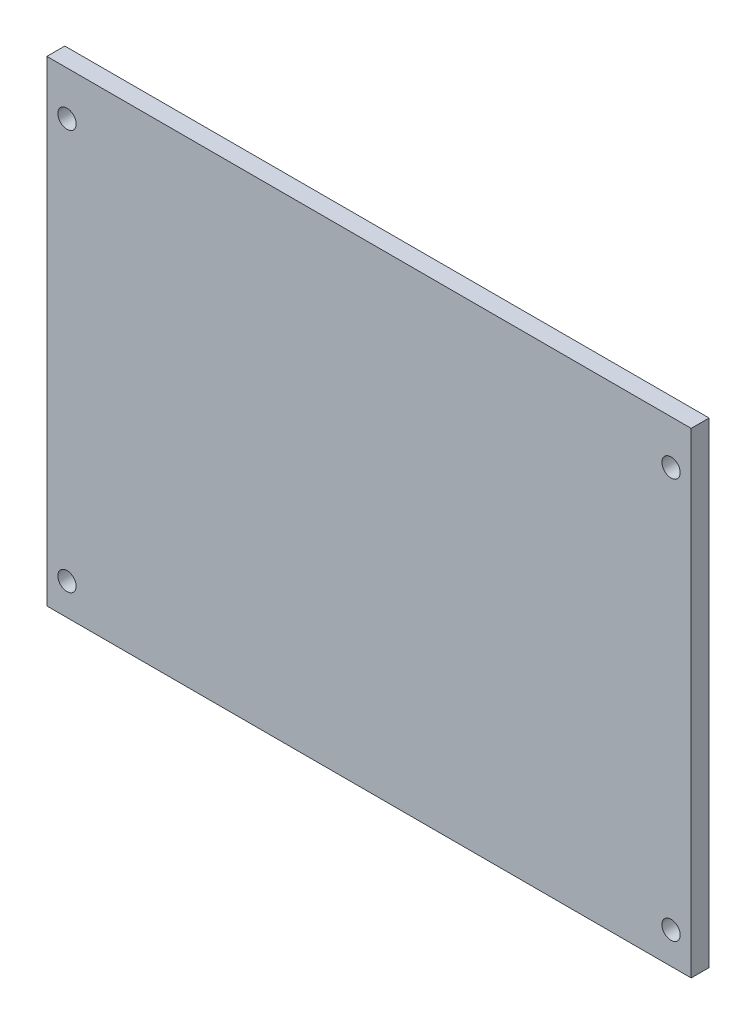
SolidWorks part; units mm, degrees
ref_plane "Front Plane" through (0, 0, 0) normal (0, 0, 1) x (1, 0, 0)
ref_plane "Top Plane" through (0, 0, 0) normal (0, 1, 0) x (1, 0, 0)
ref_plane "Right Plane" through (0, 0, 0) normal (1, 0, 0) x (0, 0, -1)
sketch "Sketch1" plane through (0, 0, 0) normal (0, 1, 0) x (1, 0, 0)
  circle A0 centre (0, 0) radius 172.5
  dimension "D1" = 345
extrude "Boss-Extrude1" add sketch "Sketch1" along normal blind 10
sketch "Sketch2" plane through (0, 10, 0) normal (0, 1, 0) x (1, 0, 0)
  circle A0 centre (-75.91, -178.72) radius 48.41
  circle A1 centre (75.91, -178.72) radius 48.41
  dimension "D1" = 96.82
  dimension "D2" = 96.82
  dimension "D3" = 151.82
  dimension "D4" = 0
  dimension "D5" = 178.72
  dimension "D6" = 75.91
extrude "Cut-Extrude1" cut sketch "Sketch2" against normal blind 10
sketch "Sketch3" plane through (0, 10, 0) normal (0, 1, 0) x (1, 0, 0)
  line L0 (-75.91, -178.72) -> (75.91, -178.72)
  line L1 (-98.9683, -119.81) -> (98.9683, -119.81)
  line L2 (0, -178.72) -> (0, -205.4095)
  line L3 (0, -116.81) -> (0, -103.1109)
  line L4 (-97.8835, -116.81) -> (97.8835, -116.81)
  arc A0 (97.8835, -116.81) -> (-97.8835, -116.81) centre (0, 0) ccw
  arc A1 (98.9683, -119.81) -> (-98.9683, -119.81) centre (0, 0) ccw
  dimension "D1" = 304.8
  dimension "D2" = 3
  dimension "D4" = 0
extrude "Boss-Extrude2" add sketch "Sketch3" along normal blind 5 contours L1 A1 A0 L4 region at (0, 10, -154.9849)
sketch "Sketch4" plane through (0, 10, 0) normal (0, 1, 0) x (1, 0, 0)
  line L0 (-28.2612, -170.1692) -> (28.2612, -170.1692)
  line L1 (28.2612, -170.1692) -> (28.2612, -183.8361)
  line L2 (28.2612, -183.8361) -> (-30.3005, -183.8361)
  line L3 (-30.3005, -183.8361) -> (-28.2612, -170.1692)
extrude "Cut-Extrude2" cut sketch "Sketch4" against normal blind 497
sketch "Sketch5" plane through (0, 10, 0) normal (0, 1, 0) x (1, 0, 0)
  line L0 (-166.525, 159.566) -> (-166.525, -120.1627)
  line L1 (166.525, 178.4393) -> (166.525, -124.881)
  line L2 (-148.2899, 170.4208) -> (120.6541, 170.4208)
  line L3 (28.2612, -170.1692) -> (-28.2612, -170.1692) construction
  line L5 (-166.525, 170.4208) -> (166.525, 170.4208)
  line L6 (-166.525, 170.4208) -> (-166.525, -186.2191)
  line L7 (-166.525, -186.2191) -> (166.525, -186.2191)
  line L8 (166.525, 170.4208) -> (166.525, -186.2191)
  line L9 (-215.4787, 226.3504) -> (214.5081, 226.3504)
  line L10 (-215.4787, 226.3504) -> (-215.4787, -259.9327)
  line L11 (-215.4787, -259.9327) -> (214.5081, -259.9327)
  line L12 (214.5081, 226.3504) -> (214.5081, -259.9327)
  arc M6 (102.8405, -138.4922) -> (-102.8405, -138.4922) centre (0, 0) ccw
  dimension "D1" = 333.05
  dimension "D2" = 166.525
  dimension "D3" = 340.59
extrude "Cut-Extrude6" cut sketch "Sketch5" against normal blind 497 contours L2 M6 | L1 M6 | L0 M6 region at (-168.9186, 10, 0) region at (0, 10, -171.2529) region at (168.9186, 10, 0)
sketch "Sketch6" plane through (0, 10, 0) normal (0, 1, 0) x (1, 0, 0)
  line L0 (-97.8835, -116.81) -> (97.8835, -116.81)
  line L1 (-97.8835, -116.81) -> (-97.8835, -61.81)
  line L2 (97.8835, -116.81) -> (97.8835, -61.81)
  line L3 (97.8835, -61.81) -> (-97.8835, -61.81)
  line L4 (92.8835, -66.81) -> (-92.8835, -66.81)
  line L5 (-92.8835, -111.81) -> (-92.8835, -66.81)
  line L6 (-92.8835, -111.81) -> (92.8835, -111.81)
  line L7 (92.8835, -111.81) -> (92.8835, -66.81)
  dimension "D1" = 55
  dimension "D2" = 5
extrude "Boss-Extrude3" add sketch "Sketch6" along normal blind 133.35
sketch "Sketch7" plane through (0, 10, 0) normal (0, 1, 0) x (1, 0, 0)
  line L1 (-92.8835, -66.81) -> (92.8835, -66.81)
  line L2 (-92.8835, -66.81) -> (-92.8835, -111.81)
  line L3 (-92.8835, -111.81) -> (92.8835, -111.81)
  line L4 (92.8835, -66.81) -> (92.8835, -111.81)
extrude "Boss-Extrude4" add sketch "Sketch7" along normal blind 5
sketch "Sketch8" plane through (0, 10, 0) normal (0, 1, 0) x (1, 0, 0)
  line L0 (-112.8835, -61.81) -> (-112.8835, -101.2671)
  line L1 (-97.8835, -61.81) -> (97.8835, -61.81)
  line L2 (-97.8835, -61.81) -> (-97.8835, -115.8298)
  line L4 (97.8835, -61.81) -> (97.8835, -115.8298)
  line L6 (112.8835, -46.81) -> (112.8835, -101.2671)
  line L7 (-88.0285, -46.81) -> (112.8835, -46.81)
  line L8 (-112.8835, -46.81) -> (-112.8835, -131.81) construction
  line L9 (-112.8835, -131.81) -> (112.8835, -131.81) construction
  line L10 (112.8835, -46.81) -> (112.8835, -131.81) construction
  line L11 (74.9923, -131.81) -> (76.4976, -131.81)
  line L12 (-97.8835, -116.81) -> (97.8835, -116.81) construction
  line L13 (97.8835, -61.81) -> (97.8835, -116.81) construction
  line L14 (-97.8835, -61.81) -> (-97.8835, -116.81) construction
  line L15 (-112.8835, -46.81) -> (112.8835, -46.81) construction
  line L18 (-112.8835, -61.81) -> (-88.0285, -61.81)
  line L19 (-88.0285, -46.81) -> (-88.0285, -61.81)
  arc A1 (-112.8835, -101.2671) -> (-96.7117, -116.81) centre (0, 0) ccw
  arc A5 (97.8835, -115.8298) -> (112.8835, -101.2671) centre (0, 0) ccw
  line M3 (-97.8835, -116.81) -> (-97.8835, -61.81)
  line M5 (97.8835, -61.81) -> (97.8835, -116.81)
  dimension "D1" = 15
extrude "Boss-Extrude5" add sketch "Sketch8" along normal blind 8 contours L0 A1 L18 M3 | A5 L6 L7 L19 L1 M5 region at (-104.9975, 10, 85.5341) region at (29.9995, 10, 60.2371)
chamfer "Chamfer1" distance 8 angle 38 3 edges at (-97.8835, 18, 88.8199) (4.9275, 18, 61.81) (97.8835, 18, 88.8199) first distance on face at (-97.8835, 51.1, 100.8157) first distance on face at (-50.228, 47.3375, 61.81) first distance on face at (97.8835, 51.1, 100.8157)
fillet "Fillet1" radius 38 3 edges at (-97.8835, 26, 88.8199) (4.9275, 26, 61.81) (97.8835, 26, 88.8199)
sketch "Sketch9" plane through (0, 10, 0) normal (0, 1, 0) x (1, 0, 0)
  circle A0 centre (0, 0) radius 374.0793
extrude "Cut-Extrude7" cut sketch "Sketch9" against normal blind 93
sketch "Sketch10" plane through (0, 10, 0) normal (0, -1, 0) x (1, 0, 0)
  circle A0 centre (0, 0) radius 152.4
  circle A1 centre (0, 0) radius 229.3861
extrude "Cut-Extrude8" cut sketch "Sketch10" against normal blind 93 and the other way blind 93
sketch "Sketch11" plane through (0, 143.35, 0) normal (0, 1, 0) x (1, 0, 0)
  line L0 (47.0835, -61.81) -> (47.0835, -116.81)
  line L1 (97.8835, -61.81) -> (-97.8835, -61.81) construction
  line L2 (-97.8835, -116.81) -> (97.8835, -116.81) construction
  line L3 (97.8835, -116.81) -> (97.8835, -61.81) construction
  line L4 (47.0835, -61.81) -> (-97.8835, -61.81)
  line L5 (-97.8835, -61.81) -> (-97.8835, -116.81)
  line L6 (-97.8835, -116.81) -> (47.0835, -116.81)
  line L8 (-140.8808, -21.3721) -> (150.5625, -21.3721)
  line L9 (-140.8808, -21.3721) -> (-140.8808, -156.1708)
  line L10 (-140.8808, -156.1708) -> (150.5625, -156.1708)
  line L11 (150.5625, -21.3721) -> (150.5625, -156.1708)
  dimension "D1" = 50.8
extrude "Cut-Extrude9" cut sketch "Sketch11" against normal blind 143
sketch "Sketch12" plane through (0, 143.35, 0) normal (0, 1, 0) x (1, 0, 0)
  line L1 (47.0835, -61.81) -> (52.0835, -61.81)
  line L2 (47.0835, -61.81) -> (47.0835, -116.81)
  line L3 (47.0835, -116.81) -> (52.0835, -116.81)
  line L4 (52.0835, -61.81) -> (52.0835, -116.81)
  dimension "D1" = 5
extrude "Boss-Extrude6" add sketch "Sketch12" against normal up to surface (133.35 mm away) up to face at (-25.4, 10, 89.31)
sketch "Sketch13" plane through (-97.8835, 0, 0) normal (-1, 0, 0) x (0, 0, 1)
  line L0 (61.81, 10) -> (116.81, 10) construction
  circle A0 centre (89.4188, 75) radius 10
  dimension "D1" = 20
  dimension "D2" = 65
extrude "Cut-Extrude10" cut sketch "Sketch13" against normal blind 58
sketch "Sketch14" plane through (0, 143.35, 0) normal (0, 1, 0) x (1, 0, 0)
  line L1 (-92.8835, -66.81) -> (47.0835, -66.81)
  line L2 (-92.8835, -66.81) -> (-92.8835, -111.81)
  line L3 (-92.8835, -111.81) -> (47.0835, -111.81)
  line L4 (47.0835, -66.81) -> (47.0835, -111.81)
extrude "Boss-Extrude7" add sketch "Sketch14" against normal blind 5
sketch "Sketch15" plane through (0, 0, 116.81) normal (0, 0, 1) x (1, 0, 0)
  line L1 (-92.8835, 138.35) -> (47.0835, 138.35)
  line L2 (-92.8835, 138.35) -> (-92.8835, 15)
  line L3 (-92.8835, 15) -> (47.0835, 15)
  line L4 (47.0835, 138.35) -> (47.0835, 15)
extrude "Cut-Extrude11" cut sketch "Sketch15" against normal blind 13
sketch "Sketch16" plane through (0, 0, 116.81) normal (0, 0, 1) x (1, 0, 0)
  line L0 (-107.8835, 143.35) -> (-107.8835, 10)
  line L1 (-92.8835, 138.35) -> (47.0835, 138.35)
  line L2 (-92.8835, 138.35) -> (-92.8835, 15)
  line L3 (-92.8835, 15) -> (47.0835, 15)
  line L4 (47.0835, 138.35) -> (47.0835, 15)
  line L6 (62.0835, 143.35) -> (62.0835, 10)
  line L8 (-107.8835, 143.35) -> (62.0835, 143.35)
  line L9 (-107.8835, 10) -> (62.0835, 10)
  line L10 (-107.8835, 153.35) -> (-107.8835, 0) construction
  line L11 (-107.8835, 0) -> (62.0835, 0) construction
  line L12 (62.0835, 153.35) -> (62.0835, 0) construction
  line L13 (-107.8835, 153.35) -> (62.0835, 153.35) construction
  line L14 (-92.8835, 76.675) -> (47.0835, 76.675)
  line L15 (-92.8835, 127.475) -> (47.0835, 127.475)
  line L16 (-92.8835, 127.475) -> (-92.8835, 25.875)
  line L17 (-92.8835, 25.875) -> (47.0835, 25.875)
  line L18 (47.0835, 127.475) -> (47.0835, 25.875)
  line L19 (-22.9, 127.475) -> (-22.9, 25.875)
  point P22 (-92.8835, 76.675)
  point P25 (-22.9, 138.35)
  line M11 (47.0835, 15) -> (-92.8835, 15)
  line M12 (-92.8835, 15) -> (-92.8835, 138.35)
  line M13 (-92.8835, 138.35) -> (47.0835, 138.35)
  line M14 (47.0835, 138.35) -> (47.0835, 15)
  line M15 (-97.8835, 10) -> (52.0835, 10)
  line M16 (52.0835, 10) -> (52.0835, 143.35)
  line M17 (52.0835, 143.35) -> (-97.8835, 143.35)
  line M18 (-97.8835, 143.35) -> (-97.8835, 10)
  dimension "D2" = 101.6
  dimension "D3" = 0
  dimension "D4" = 0
  dimension "D5" = 0
  dimension "D1" = 15
extrude "Boss-Extrude9" add sketch "Sketch16" against normal blind 17 contours L0 L9 L8 M18 | L4 L2 M18 M15 M16 M17 M14 M11 M12 M13 | L9 L6 L8 M16 | L15 M12 M14 M13 | L17 M12 M11 M14 region at (-102.8835, 76.675, 116.81) region at (-22.9, 141.3432, 116.81) region at (57.0835, 76.675, 116.81) region at (-22.9, 132.9125, 116.81) region at (-22.9, 20.4375, 116.81)
sketch "Sketch17" plane through (0, 0, 116.81) normal (0, 0, 1) x (1, 0, 0)
  line L0 (-95.8835, 130.475) -> (-95.8835, 22.875)
  line L1 (-92.8835, 127.475) -> (47.0835, 127.475)
  line L2 (-92.8835, 127.475) -> (-92.8835, 25.875)
  line L3 (-92.8835, 25.875) -> (47.0835, 25.875)
  line L4 (47.0835, 127.475) -> (47.0835, 25.875)
  line L5 (-95.8835, 22.875) -> (50.0835, 22.875)
  line L6 (50.0835, 130.475) -> (50.0835, 22.875)
  line L7 (-95.8835, 130.475) -> (50.0835, 130.475)
  line L8 (-99.8835, 134.475) -> (54.0835, 134.475)
  line L9 (54.0835, 134.475) -> (54.0835, 18.875)
  line L10 (-99.8835, 18.875) -> (54.0835, 18.875)
  line L11 (-99.8835, 134.475) -> (-99.8835, 18.875)
  dimension "D1" = 3
  dimension "D2" = 4
extrude "Cut-Extrude12" cut sketch "Sketch17" against normal blind 10 contours L8 L11 L10 L9 L0 L7 L6 L5 region at (-22.9, 132.5497, 116.81)
sketch "Sketch20" plane through (0, 0, 116.81) normal (0, 0, 1) x (1, 0, 0)
  line L0 (-107.8835, 143.35) -> (-107.8835, 10) construction
  line L1 (-110.8835, 146.35) -> (65.0835, 146.35)
  line L2 (-110.8835, 146.35) -> (-110.8835, 7)
  line L3 (-110.8835, 7) -> (65.0835, 7)
  line L4 (65.0835, 146.35) -> (65.0835, 7)
  line L5 (62.0835, 143.35) -> (62.0835, 10) construction
  line L6 (-107.8835, 10) -> (62.0835, 10) construction
  line L7 (-107.8835, 143.35) -> (62.0835, 143.35) construction
  line L9 (-107.8835, 143.35) -> (62.0835, 143.35)
  line L10 (-107.8835, 143.35) -> (-107.8835, 10)
  line L11 (-107.8835, 10) -> (62.0835, 10)
  line L12 (62.0835, 143.35) -> (62.0835, 10)
  line L13 (-110.8835, 7) -> (65.0835, 7)
  line L14 (-110.8835, 7) -> (-110.8835, 13.35)
  line L15 (-110.8835, 13.35) -> (65.0835, 13.35)
  line L16 (65.0835, 7) -> (65.0835, 13.35)
  line M13 (-107.8835, 10) -> (62.0835, 10)
  line M14 (62.0835, 10) -> (62.0835, 143.35)
  dimension "D1" = 3
  dimension "D2" = 3
  dimension "D3" = 3
  dimension "D4" = 3
  dimension "D5" = 6.35
chamfer "Chamfer2" distance 10 angle 30 2 edges at (-22.9, 25.875, 99.81) (-22.9, 127.475, 99.81) first distance on face at (-22.9, 25.875, 108.31) first distance on face at (-22.9, 132.9125, 99.81)
sketch "Sketch24" plane through (-97.8835, 0, 0) normal (-1, 0, 0) x (0, 0, 1)
  line L0 (99.81, 143.35) -> (99.81, 10) construction
  circle A1 centre (83.81, 75) radius 15
  dimension "D1" = 30
  dimension "D2" = 16
extrude "Cut-Extrude16" cut sketch "Sketch24" against normal blind 177.5
extrude "Cut-Extrude17" cut sketch "Sketch20" against normal blind 177.5 contours L15 L2 L3 L4 L10 M14 M13 | L15 L10 M13 M14 region at (-22.9, 8.6165, 116.81) region at (-22.9, 11.675, 116.81)
sketch "Sketch25" plane through (0, 13.35, 0) normal (0, -1, 0) x (-1, 0, 0)
  line L1 (-47.0835, -66.81) -> (92.8835, -66.81)
  line L2 (-47.0835, -66.81) -> (-47.0835, -105.5835)
  line L3 (-47.0835, -105.5835) -> (92.8835, -105.5835)
  line L4 (92.8835, -66.81) -> (92.8835, -105.5835)
extrude "Boss-Extrude11" add sketch "Sketch25" against normal blind 5
sketch "Sketch26" plane through (0, 0, 116.81) normal (0, 0, 1) x (1, 0, 0)
  line L0 (-107.8835, 143.35) -> (-107.8835, 13.35) construction
  line L1 (-110.8835, 143.35) -> (-107.8835, 143.35)
  line L2 (-110.8835, 143.35) -> (-110.8835, 13.35)
  line L3 (-110.8835, 13.35) -> (-107.8835, 13.35)
  line L4 (65.0835, 143.35) -> (65.0835, 13.35)
  line L5 (62.0835, 143.35) -> (62.0835, 13.35) construction
  line L6 (62.0835, 13.35) -> (65.0835, 13.35)
  line L8 (-107.8835, 143.35) -> (-107.8835, 13.35)
  line L10 (62.0835, 143.35) -> (62.0835, 13.35)
  line L11 (62.0835, 143.35) -> (65.0835, 143.35)
  dimension "D1" = 3
  dimension "D2" = 3
extrude "Boss-Extrude12" add sketch "Sketch26" against normal up to surface (17 mm away) up to face at (57.0835, 78.35, 99.81)
sketch "Sketch18" plane through (0, 0, 116.81) normal (0, 0, 1) x (1, 0, 0)
  line L7 (-99.8835, 134.475) -> (-99.8835, 18.875) construction
  line L8 (54.0835, 134.475) -> (54.0835, 18.875) construction
  circle A2 centre (-105.3835, 22) radius 2.5
  circle A3 centre (59.5835, 22) radius 2.5
  circle A4 centre (59.5835, 131.35) radius 2.5
  circle A5 centre (-105.3835, 131.35) radius 2.5
  point P10 (-22.9, 76.675)
  dimension "D4" = 5
  dimension "D5" = 5
  dimension "D10" = 5.5
  dimension "D12" = 5.5
extrude "Cut-Extrude19" cut sketch "Sketch18" against normal blind 26
sketch "Sketch27" plane through (0, 0, 116.81) normal (0, 0, 1) x (1, 0, 0)
  line L0 (-99.1835, 133.775) -> (-99.1835, 19.575)
  line L1 (-99.8835, 134.475) -> (54.0835, 134.475)
  line L2 (-99.8835, 134.475) -> (-99.8835, 18.875)
  line L3 (-99.8835, 18.875) -> (54.0835, 18.875)
  line L4 (54.0835, 134.475) -> (54.0835, 18.875)
  line L5 (-99.1835, 19.575) -> (53.3835, 19.575)
  line L6 (53.3835, 133.775) -> (53.3835, 19.575)
  line L7 (-99.1835, 133.775) -> (53.3835, 133.775)
  line L8 (46.3835, 26.575) -> (46.3835, 126.775)
  line L9 (-95.8835, 130.475) -> (50.0835, 130.475)
  line L10 (-95.8835, 130.475) -> (-95.8835, 22.875)
  line L11 (-95.8835, 22.875) -> (50.0835, 22.875)
  line L12 (50.0835, 130.475) -> (50.0835, 22.875)
  line L13 (47.0835, 25.875) -> (-92.8835, 25.875)
  line L14 (47.0835, 25.875) -> (47.0835, 127.475)
  line L15 (47.0835, 127.475) -> (-92.8835, 127.475)
  line L16 (-92.8835, 25.875) -> (-92.8835, 127.475)
  line L17 (46.3835, 126.775) -> (-92.1835, 126.775)
  line L18 (-92.1835, 26.575) -> (-92.1835, 126.775)
  line L19 (46.3835, 26.575) -> (-92.1835, 26.575)
  line L20 (-96.5835, 131.175) -> (50.7835, 131.175)
  line L21 (50.7835, 131.175) -> (50.7835, 22.175)
  line L22 (-96.5835, 22.175) -> (50.7835, 22.175)
  line L23 (-96.5835, 131.175) -> (-96.5835, 22.175)
  dimension "D1" = 0.7
  dimension "D2" = 0.7
  dimension "D3" = 0.7
extrude "Boss-Extrude13" add sketch "Sketch27" against normal blind 8.45 separate body contours L7 L0 L5 L6 L23 L20 L21 L22 | L19 L8 L17 L18 region at (-22.9, 131.8693, 116.81) region at (-22.9, 76.675, 116.81)
sketch "Sketch28" plane through (0, 0, 116.81) normal (0, 0, 1) x (1, 0, 0)
  line L1 (-110.8835, 143.35) -> (65.0835, 143.35)
  line L2 (-110.8835, 143.35) -> (-110.8835, 13.35)
  line L3 (-110.8835, 13.35) -> (65.0835, 13.35)
  line L4 (65.0835, 143.35) -> (65.0835, 13.35)
  circle A0 centre (-105.3835, 131.35) radius 2.5
  circle A1 centre (59.5835, 131.35) radius 2.5
  circle A2 centre (59.5835, 22) radius 2.5
  circle A3 centre (-105.3835, 22) radius 2.5
extrude "Boss-Extrude14" add sketch "Sketch28" along normal blind 5
sketch "Sketch29" plane through (0, 0, 61.81) normal (0, 0, -1) x (-1, 0, 0)
  line L1 (-138.5926, 160.545) -> (153.936, 160.545)
  line L2 (-138.5926, 160.545) -> (-138.5926, -10.7704)
  line L3 (-138.5926, -10.7704) -> (153.936, -10.7704)
  line L4 (153.936, 160.545) -> (153.936, -10.7704)
extrude "Cut-Extrude20" cut sketch "Sketch29" against normal up to surface (46.55 mm away) up to face at (-22.9, 76.675, 108.36)
sketch "Sketch30" plane through (0, 0, 108.36) normal (0, 0, -1) x (-1, 0, 0)
  line L1 (-65.0835, 143.35) -> (110.8835, 143.35)
  line L2 (-65.0835, 143.35) -> (-65.0835, 13.35)
  line L3 (-65.0835, 13.35) -> (110.8835, 13.35)
  line L4 (110.8835, 143.35) -> (110.8835, 13.35)
  line L5 (-46.3835, 126.775) -> (92.1835, 126.775)
  line L6 (-46.3835, 126.775) -> (-46.3835, 26.575)
  line L7 (-46.3835, 26.575) -> (92.1835, 26.575)
  line L8 (92.1835, 126.775) -> (92.1835, 26.575)
  line L9 (95.8835, 22.875) -> (-50.0835, 22.875)
  line L10 (95.8835, 22.875) -> (95.8835, 130.475)
  line L11 (95.8835, 130.475) -> (-50.0835, 130.475)
  line L12 (-50.0835, 22.875) -> (-50.0835, 130.475)
  line L13 (-54.0835, 134.475) -> (99.8835, 134.475)
  line L14 (-54.0835, 134.475) -> (-54.0835, 18.875)
  line L15 (-54.0835, 18.875) -> (99.8835, 18.875)
  line L16 (99.8835, 134.475) -> (99.8835, 18.875)
  line M1 (-46.3835, 26.575) -> (92.1835, 26.575)
  line M2 (92.1835, 26.575) -> (92.1835, 126.775)
  line M3 (92.1835, 126.775) -> (-46.3835, 126.775)
  line M4 (-46.3835, 126.775) -> (-46.3835, 26.575)
extrude "Cut-Extrude23" cut sketch "Sketch30" against normal offset from surface (8.55 mm away) 4.9 contours L12 L9 L10 L11 M1 M4 M3 M2 | L4 L1 L2 L3 L13 L16 L15 L14 region at (-22.9, 141.1622, 108.36) region at (-22.9, 24.6884, 108.36) up to face at (62.0835, 22, 121.81)
